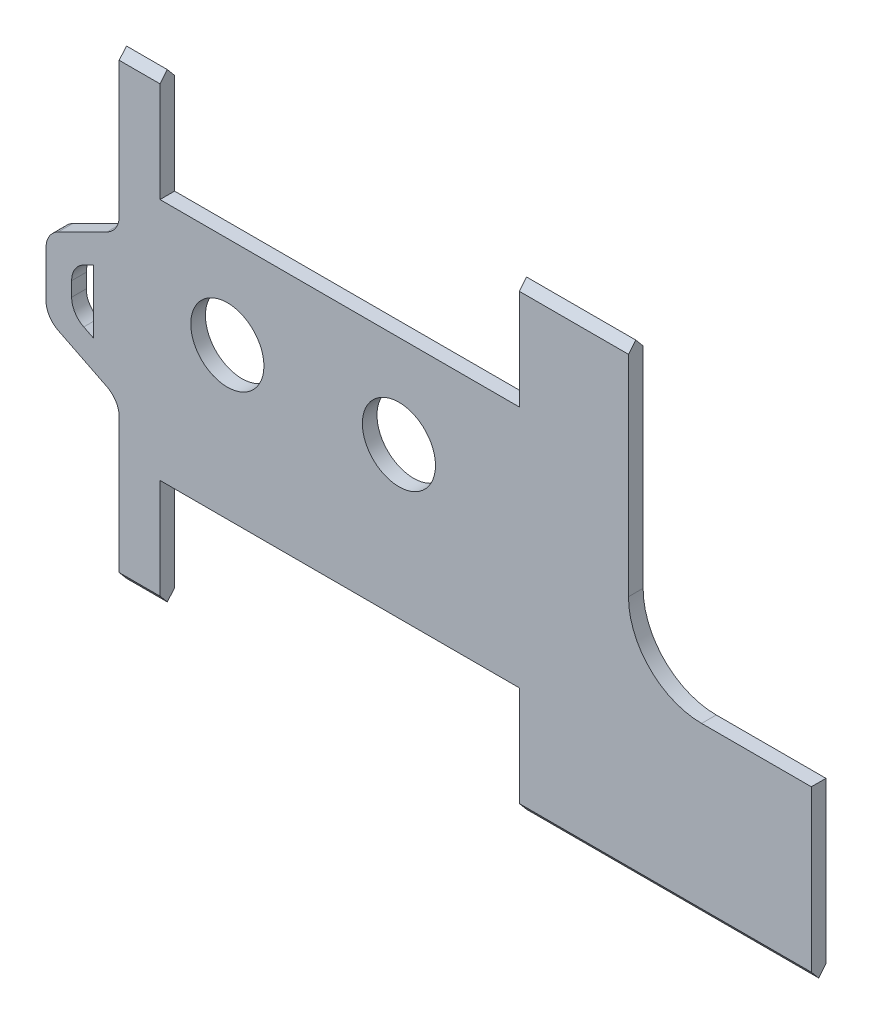
SolidWorks part; units mm, degrees
ref_plane "Front Plane" through (0, 0, 0) normal (0, 0, 1) x (1, 0, 0)
ref_plane "Top Plane" through (0, 0, 0) normal (0, 1, 0) x (1, 0, 0)
ref_plane "Right Plane" through (0, 0, 0) normal (1, 0, 0) x (0, 0, -1)
sketch "Sketch1" plane through (0, 0, 11.1483) normal (0, 0, 1) x (1, 0, 0)
  line L0 (22.423, 106.8975) -> (12.423, 101.8975)
  line L5 (22.223, 125.272) -> (22.223, 68.523) construction
  line L10 (12.423, 101.8975) -> (12.423, 91.8975)
  line L11 (117.248, 128.723) -> (22.223, 128.723) construction
  line L12 (117.248, 128.723) -> (117.248, 65.072) construction
  line L13 (117.248, 65.072) -> (22.223, 65.072) construction
  line L14 (22.223, 128.723) -> (22.223, 65.072) construction
  line L15 (117.048, 128.523) -> (22.423, 128.523)
  line L16 (22.423, 128.523) -> (22.423, 65.272)
  line L17 (117.048, 65.272) -> (22.423, 65.272)
  line L18 (117.048, 128.523) -> (117.048, 65.272)
  line L19 (12.423, 91.8975) -> (22.423, 86.8975)
  line L20 (92.048, 128.523) -> (92.048, 88.523)
  line L21 (92.048, 88.523) -> (117.048, 88.523)
  line L25 (22.423, 106.8975) -> (22.423, 86.8975)
  line L26 (15.923, 94.0606) -> (18.923, 92.5606)
  line L27 (18.923, 101.2344) -> (18.923, 92.5606)
  line L28 (18.923, 101.2344) -> (15.923, 99.7344)
  line L29 (15.923, 99.7344) -> (15.923, 94.0606)
  line L30 (-882.952, 96.8975) -> (49117.048, 96.8975) construction
  line L31 (28.005, 130.223) -> (28.005, 127.223) construction
  line L32 (28.005, 128.523) -> (77.123, 128.523)
  line L33 (28.005, 128.523) -> (28.005, 113.523)
  line L34 (28.005, 113.523) -> (77.123, 113.523)
  line L35 (77.123, 128.523) -> (77.123, 113.523)
  line L37 (77.123, 130.223) -> (77.123, 127.223) construction
  line L38 (28.005, 80.272) -> (77.123, 80.272)
  line L39 (77.123, 65.272) -> (77.123, 80.272)
  line L40 (28.005, 65.272) -> (77.123, 65.272)
  line L41 (28.005, 65.272) -> (28.005, 80.272)
  circle A0 centre (37.211, 100.9142) radius 5
  circle A1 centre (60.6662, 100.8556) radius 5
  point P4 (22.423, 96.8975)
  point P8 (12.423, 96.8975)
  point P34 (117.048, 96.8975)
  point P40 (77.123, 128.523)
  dimension "D7" = 10
  dimension "D8" = 10
  dimension "D1" = 0.2
  dimension "D2" = 10
  dimension "D3" = 10
  dimension "D4" = 20
  dimension "D5" = 40
  dimension "D6" = 25
  dimension "D9" = 3.5
  dimension "D10" = 15
extrude "Boss-Extrude1" add sketch "Sketch1" along normal mid plane 2 contours L18 L15 L16 L17 | L10 L19 L16 L0 region at (22.1994, 96.8975, 11.1483) region at (67.8745, 93.2451, 11.1483)
sketch "Sketch2" plane through (22.423, 0, 0) normal (-1, 0, 0) x (0, 0, 1)
  line L5 (-986.1517, 96.8975) -> (49013.8483, 96.8975) construction
  line L6 (13.8483, 68.523) -> (13.8483, 125.272) construction
  line L7 (10.1013, 128.523) -> (10.1013, 127.1682)
  line L8 (12.1953, 127.1682) -> (11.1483, 128.4124)
  line L10 (12.1953, 66.6268) -> (12.1953, 65.272)
  line L11 (12.1953, 65.272) -> (10.1013, 65.272)
  line L12 (11.1483, 65.3826) -> (10.1013, 66.6268)
  line L13 (12.1953, 66.6268) -> (11.1483, 65.3826)
  line L14 (11.1483, 65.3826) -> (10.1013, 66.6268)
  line L15 (12.1953, 66.6268) -> (11.1483, 65.3826)
  line L16 (10.1013, 65.272) -> (10.1013, 66.6268)
  line L17 (12.1483, 65.272) -> (10.1483, 65.272) construction
  line L18 (11.1483, 128.4124) -> (10.1013, 127.1682)
  line L19 (12.1953, 128.523) -> (10.1013, 128.523)
  line L20 (12.1953, 127.1682) -> (12.1953, 128.523)
  point P9 (13.8483, 96.8975)
  dimension "D2" = 0.2
extrude "Cut-Extrude1" cut sketch "Sketch2" against normal through all
fillet "Fillet1" radius 10 1 edges at (92.048, 88.523, 11.1483)
fillet "Fillet2" radius 3 6 edges at (15.923, 99.7344, 11.1483) (15.923, 94.0606, 11.1483) (22.423, 106.8975, 11.1483) (12.423, 101.8975, 11.1483) (12.423, 91.8975, 11.1483) (22.423, 86.8975, 11.1483)
